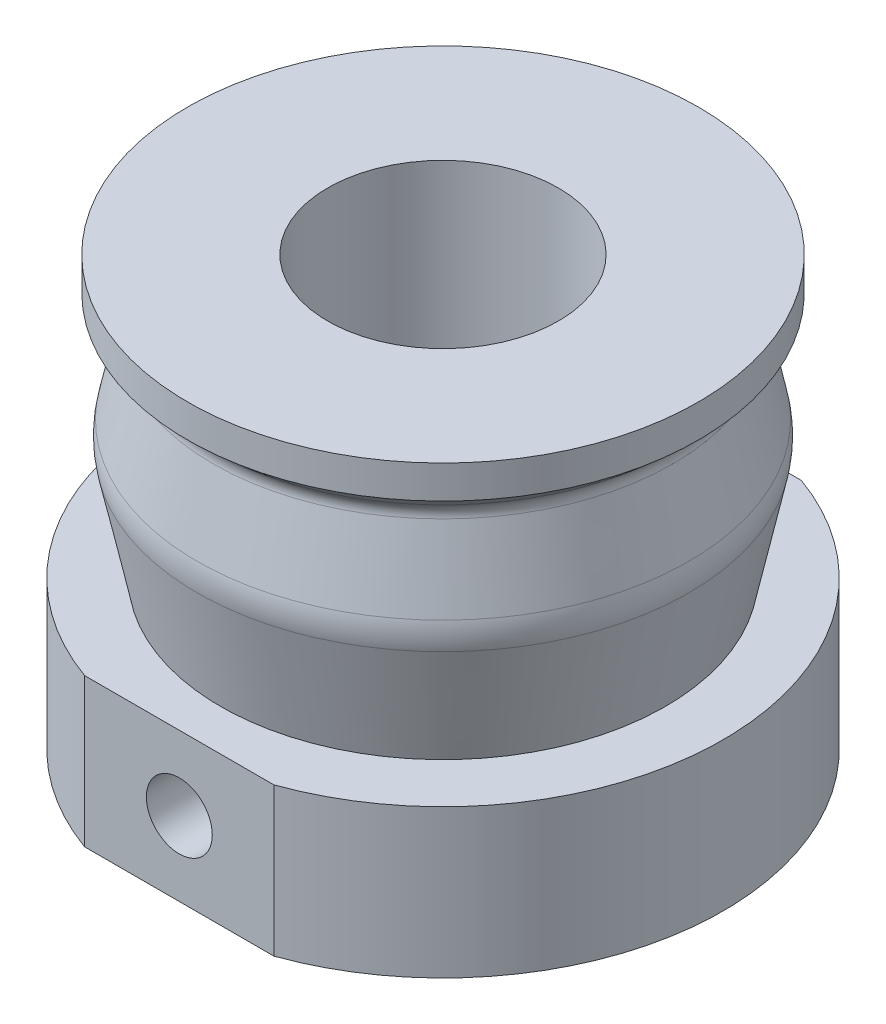
SolidWorks part; units mm, degrees
ref_plane "Front Plane" through (0, 0, 0) normal (0, 0, 1) x (1, 0, 0)
ref_plane "Top Plane" through (0, 0, 0) normal (0, 1, 0) x (1, 0, 0)
ref_plane "Right Plane" through (0, 0, 0) normal (1, 0, 0) x (0, 0, -1)
sketch "Sketch2" plane through (0, 0, 0) normal (0, 0, 1) x (1, 0, 0)
  line L0 (0, 0) -> (0, 15.6064) construction
  line L1 (3.5, 0) -> (3.5, 13)
  line L2 (3.5, 13) -> (7.75, 13)
  line L3 (7.75, 13) -> (7.75, 12)
  line L4 (7.75, 12) -> (6.75, 12)
  line L5 (6.75, 12) -> (7.4566, 8.6645)
  line L6 (7.4566, 7.8355) -> (6.75, 4.5)
  line L7 (6.75, 4.5) -> (8.5, 4.5)
  line L8 (8.5, 4.5) -> (8.5, 0)
  line L9 (8.5, 0) -> (3.5, 0)
  arc A0 (7.4566, 8.6645) -> (7.4566, 7.8355) centre (5.5, 8.25) cw
  point P16 (7.5, 8.25)
  dimension "D7" = 2
  dimension "D1" = 7
  dimension "D2" = 13
  dimension "D3" = 1
  dimension "D4" = 17
  dimension "D5" = 15
  dimension "D6" = 0.75
  dimension "D8" = 4.5
  dimension "D9" = 1
revolve "Revolve1" add sketch "Sketch2" angle 360 about L0
sketch "Sketch3" plane through (0, 0, 0) normal (0, -1, 0) x (1, 0, 0)
  line L0 (-2.8723, 8) -> (2.8723, 8)
  line L1 (0, 0) -> (0, 8) construction
  circle A0 centre (0, 0) radius 8.5 construction
  arc A1 (2.8723, 8) -> (-2.8723, 8) centre (0, 0) ccw
  point P4 (0, 8.5)
  dimension "D1" = 0.5
extrude "Cut-Extrude1" cut sketch "Sketch3" against normal up to surface (4.5 mm away) up to face at (0, 4.5, -6.75)
sketch "Sketch4" plane through (0, 0, 8) normal (0, 0, 1) x (1, 0, 0)
  line L0 (0, 0) -> (0, 4.5) construction
  line L1 (-2.8723, 0) -> (2.8723, 0) construction
  line L2 (-2.8723, 4.5) -> (2.8723, 4.5) construction
  point P6 (0, 2.25)
hole_wizard "Ø2.0mm Dowel Hole1" positions "Sketch6" profile "Sketch5" hole size "Ø2.0" standard "ANSI Metric"
sketch "Sketch6" plane through (0, 0, 8) normal (0, 0, 1) x (1, 0, 0)
  point P0 (0, 2.25)
sketch "Sketch5" plane through (0, 2.25, 8) normal (1, 0, 0) x (0, -1, 0)
  line L0 (0, 0) -> (0, 6.6009)
  line L1 (0, 6.6009) -> (1, 6)
  line L2 (1, 6) -> (1, 0)
  line L5 (1, 0) -> (0, 0)
  line L10 (0, 6.6009) -> (-1, 6) construction
  line L11 (0, -6.35) -> (0, 107.95) construction
  dimension "Hole Dia." = 2
  dimension "Hole Depth" = 6
  dimension "Drill Angle" = 118
mirror "Mirror1" about plane through (0, 0, 0) normal (0, 0, 1) of "Ø2.0mm Dowel Hole1", "Cut-Extrude1"
fillet "Fillet1" [suppressed] radius 1.5
chamfer "Chamfer1" distance 1 distance2 0.75 1 edges at (0, 12, -6.75) first distance on face at (0, 12, -7.75)
fillet "Fillet2" radius 0.5 1 edges at (0, 11.2663, -6.9054)
